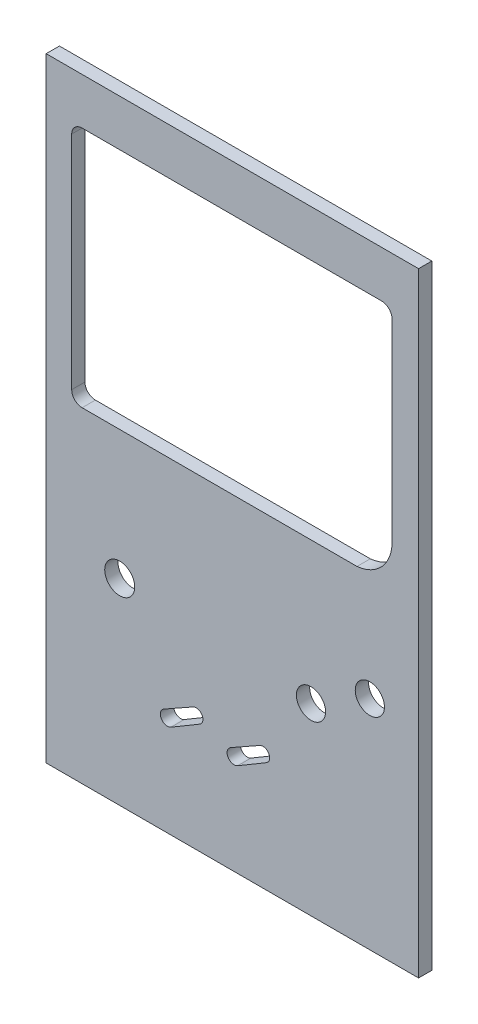
SolidWorks part; units mm, degrees
ref_plane "Front Plane" through (0, 0, 0) normal (0, 0, 1) x (1, 0, 0)
ref_plane "Top Plane" through (0, 0, 0) normal (0, 1, 0) x (1, 0, 0)
ref_plane "Right Plane" through (0, 0, 0) normal (1, 0, 0) x (0, 0, -1)
sketch "Sketch1" plane through (0, 0, 0) normal (0, 0, 1) x (1, 0, 0)
  line L0 (0.1058, 73.6301) -> (-0.0148, 62.4901) construction
  line L1 (-0.0148, 62.4901) -> (-0.0148, 56.2001) construction
  line L2 (-0.0148, 56.2001) -> (-0.0148, 10.268) construction
  line L3 (-15.4692, -49.8142) -> (-8.5409, -45.8142) construction
  line L4 (-15.4692, -49.8142) -> (0.5308, -49.8142) construction
  line L5 (0.5308, -49.8142) -> (7.4591, -45.8142) construction
  line L6 (-0.0148, 10.268) -> (0.1058, -73.6642) construction
  line L15 (-16.3293, -29.1587) -> (-16.3293, -23.8757)
  line L20 (-0.2968, -48.3429) -> (6.6759, -44.4208)
  line L21 (8.2583, -47.1985) -> (1.3584, -51.2855)
  line L22 (-44.5392, 73.6301) -> (44.7508, 73.6301)
  line L23 (44.7508, 73.6301) -> (44.7508, -73.6642)
  line L24 (44.7508, -73.6642) -> (-44.5392, -73.6642)
  line L25 (-44.5392, -73.6642) -> (-44.5392, 73.6301)
  line L26 (-25.0598, 56.2001) -> (-25.0598, 10.268)
  line L27 (-25.0598, 10.268) -> (25.0303, 10.268)
  line L28 (25.0303, 10.268) -> (25.0303, 56.2001)
  line L29 (25.0303, 56.2001) -> (-25.0598, 56.2001)
  line L34 (35.8896, 62.4901) -> (-35.9192, 62.4901)
  line L35 (-38.4192, 59.9901) -> (-38.4192, 6.918)
  line L36 (-35.9192, 4.418) -> (29.9974, 4.418)
  line L37 (38.3896, 13.668) -> (38.3896, 59.9901)
  line L38 (-16.2968, -48.3429) -> (-9.3241, -44.4208)
  line L39 (-7.7417, -47.1985) -> (-14.6416, -51.2855)
  line L150 (42.2525, -55.0539) -> (42.2511, -54.9499)
  circle A2 centre (-26.9008, -26.5172) radius 3.6
  arc A3 (8.2583, -47.1985) -> (6.6759, -44.4208) centre (7.4591, -45.8142) ccw
  arc A6 (-16.2968, -48.3429) -> (-14.6416, -51.2855) centre (-15.4692, -49.8142) ccw
  arc A7 (-7.7417, -47.1985) -> (-9.3241, -44.4208) centre (-8.5409, -45.8142) ccw
  circle A15 centre (18.9576, -29.5613) radius 3.5
  circle A16 centre (33.0683, -21.4917) radius 3.5
  arc A17 (-0.2968, -48.3429) -> (1.3584, -51.2855) centre (0.5308, -49.8142) ccw
  circle A19 centre (-32.8459, 40.326) radius 4.5
  arc A24 (38.3896, 59.9901) -> (35.8896, 62.4901) centre (35.8896, 59.9901) ccw
  arc A25 (-35.9192, 62.4901) -> (-38.4192, 59.9901) centre (-35.9192, 59.9901) ccw
  arc A26 (-38.4192, 6.918) -> (-35.9192, 4.418) centre (-35.9192, 6.918) ccw
  arc A27 (29.9974, 4.418) -> (38.3896, 13.668) centre (29.1397, 13.6282) ccw
  dimension "D4" = 11.14
  dimension "D8" = 7
  dimension "D11" = 9
  dimension "D12" = 7.2
  dimension "D14" = 9.25
  dimension "D15" = 2.5
  dimension "D2" = 89.29
  dimension "D3" = 147.2943
  dimension "D5" = 25.9097
  dimension "D6" = 8.0696
  dimension "D7" = 14.1107
  dimension "D9" = 7.7861
  dimension "D10" = 22.1641
  dimension "D13" = 10.5715
  dimension "D16" = 6.29
  dimension "D17" = 6.12
  dimension "D18" = 5.85
  dimension "D19" = 16
  dimension "D20" = 8
  dimension "D21" = 29.07
  dimension "D22" = 23.85
  dimension "D23" = 30
extrude "Body" add sketch "Sketch1<7>" along normal blind 3.18 contours L25 L24 L23 L22 A27 L36 A26 L35 A25 L34 A24 L37 A17 L20 A3 L21 A16 A15 A7 L39 A6 L38 A2 region at (0.1688, -16.746, 0)
sketch "Sketch1<7>" plane through (0, 0, 0) normal (0, 0, 1) x (1, 0, 0) same geometry as "Sketch1"
extrude "Buttons" [suppressed] add sketch "Sketch1" along normal blind 3.18 contours A19 | A2 | L39 A7 L38 A6 | L20 A17 L21 A3 | A15 | A16
